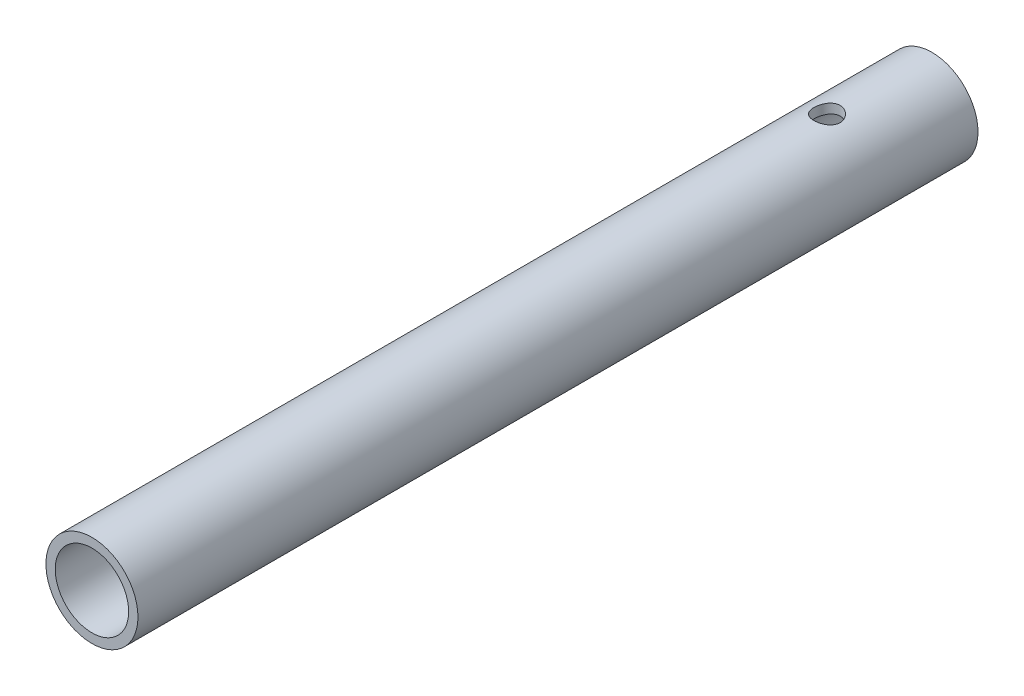
SolidWorks part; units mm, degrees
ref_plane "Front Plane" through (0, 0, 0) normal (0, 0, 1) x (1, 0, 0)
ref_plane "Top Plane" through (0, 0, 0) normal (0, 1, 0) x (1, 0, 0)
ref_plane "Right Plane" through (0, 0, 0) normal (1, 0, 0) x (0, 0, -1)
sketch "Sketch1" plane through (0, 0, 0) normal (0, 0, 1) x (1, 0, 0)
  line L0 (13.3223, 0) -> (16.7005, 0) construction
  circle A0 centre (0, 0) radius 16.7005
  circle A1 centre (0, 0) radius 13.3223
  dimension "OD" = 33.401
  dimension "ID" = 26.6446
  dimension "Wall Thickness" = 3.3782
sketch "Sketch2" plane through (0, 0, 0) normal (0, 0, 1) x (1, 0, 0)
  circle A1 centre (0, 0) radius 13.3223
  circle A3 centre (0, 0) radius 13.3223
  circle A5 centre (0, 0) radius 16.7005
  circle A6 centre (0, 0) radius 16.7005
  dimension "D1" = 0
  dimension "D2" = 0
extrude "Pipe Extrude" add sketch "Sketch2" along normal mid plane 304.8
ref_axis "Center Axis 1" through (-670.56, 0, 0) along (1, 0, 0)
ref_axis "Center Axis 2" through (0, 18.3845, 0) along (0, -1, 0)
ref_plane "Plane1" through (0, 0, -152.4) normal (0, 0, -1) x (-1, 0, 0)
ref_plane "Plane2" through (0, 0, 152.4) normal (0, 0, 1) x (1, 0, 0)
sketch "Sketch3" plane through (0, 0, 0) normal (0, 1, 0) x (1, 0, 0)
  circle A0 centre (0, 114.3) radius 4.7625
  point P2 (0, 0)
  dimension "D1" = 9.525
  dimension "D2" = 114.3
extrude "Cut-Extrude1" cut sketch "Sketch3" against normal through all both and the other way through all
